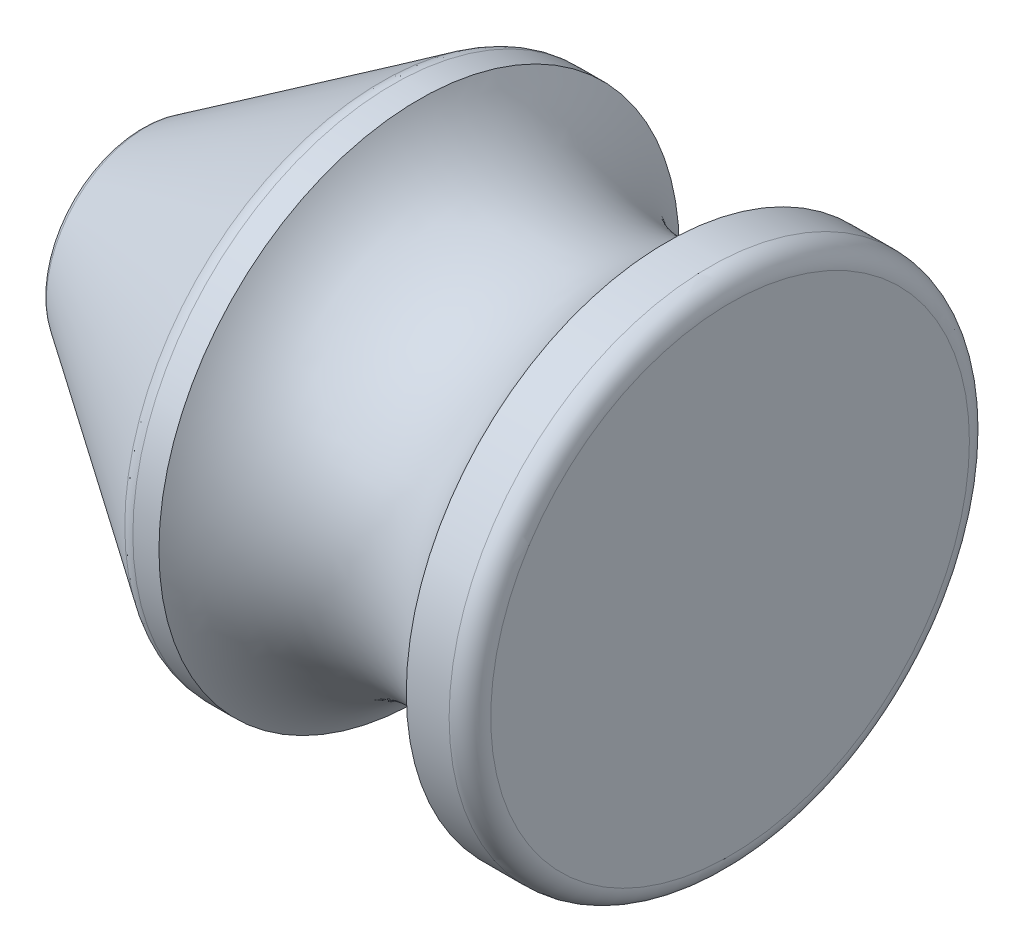
SolidWorks part; units mm, degrees
ref_plane "Alzado" through (0, 0, 0) normal (1, 0, 0) x (0, 1, 0)
ref_plane "Planta" through (0, 0, 0) normal (0, 0, 1) x (0, 1, 0)
ref_plane "Vista lateral" through (0, 0, 0) normal (0, 1, 0) x (-1, 0, 0)
sketch "Croquis1" plane through (0, 0, 0) normal (1, 0, 0) x (0, 1, 0)
  line L0 (1.8974, 1.3) -> (-1.8974, 1.3)
  circle A0 centre (0, 0) radius 12.5
  circle A1 centre (0, 0) radius 2.3
  point P5 (0, -2.3)
  dimension "D1" = 25
  dimension "D2" = 4.6
  dimension "D3" = 3.6
extrude "Saliente-Extruir1" add sketch "Croquis1" along normal blind 9 and the other way blind 19.5 contours A0 A1 | L0 A1 region at (0, 0, 1.7085) region at (0, -12.1464, 0)
sketch "Croquis2" plane through (0, 0, 0) normal (0, 1, 0) x (-1, 0, 0)
  line L1 (-7.5177, 0) -> (7.5177, 0) construction
  line L3 (0, 16.2) -> (0, 13.2453) construction
  circle A0 centre (0, 16.2) radius 7
  point P2 (0, 15)
  point P10 (0, 0)
  dimension "D1" = 14
  dimension "D2" = 16.2
revolve "Cortar-Revolución1" cut sketch "Croquis2" angle 360 about L1
chamfer "Chaflán1" distance 8 distance2 12 1 edges at (-19.5, 0, -12.5) first distance on face at (-19.5, 0, -0.5)
fillet "Redondeo1" radius 1 2 edges at (-7.5, 0, -12.5) (-19.5, 0, -4.5)
fillet "Redondeo2" radius 1 1 edges at (9, 0, -12.5)
extrude "Saliente-Extruir2" add sketch "Croquis1<3>" against normal blind 12 from surface contours L0 A1 region at (0, 0, -0.3263) starting at face at (9, 0, -11.5)
sketch "Croquis1<3>" plane through (0, 0, 0) normal (1, 0, 0) x (0, 1, 0) same geometry as "Croquis1"
